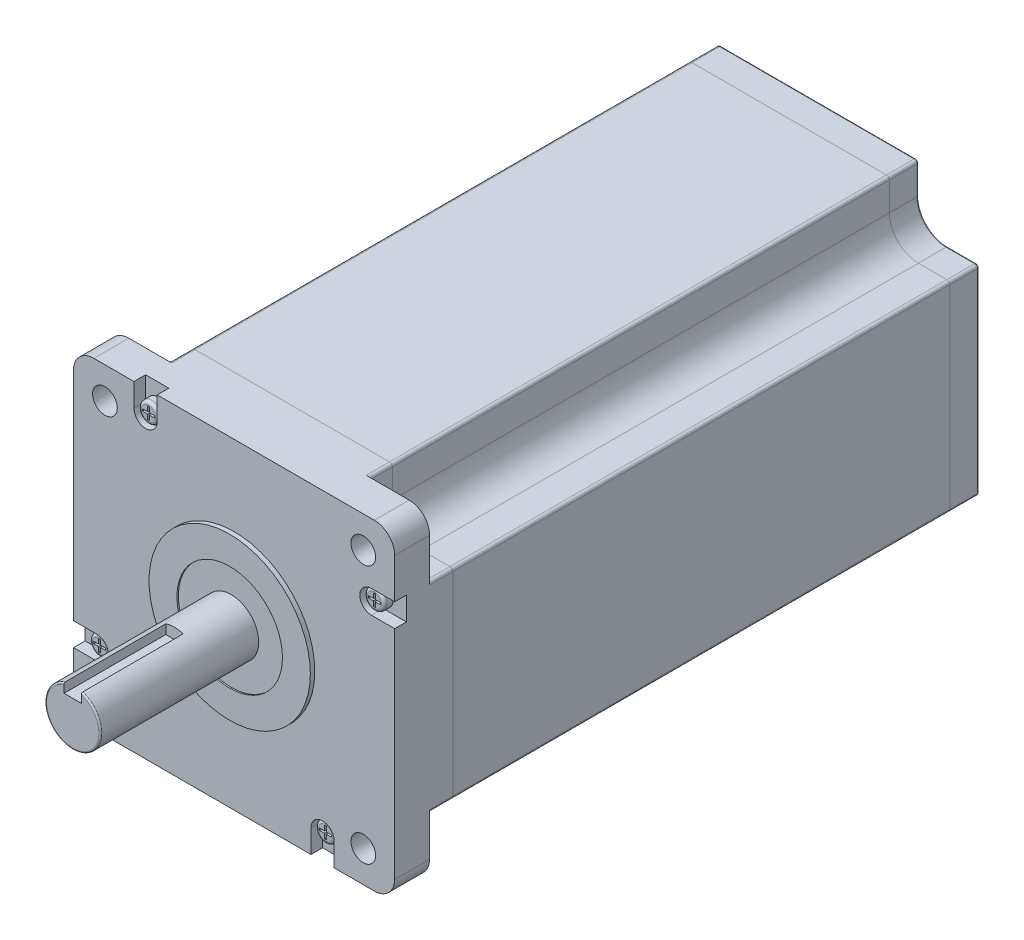
SolidWorks part; units mm, degrees
ref_plane "Front Plane" through (0, 0, 0) normal (0, 0, 1) x (1, 0, 0)
ref_plane "Top Plane" through (0, 0, 0) normal (0, 1, 0) x (1, 0, 0)
ref_plane "Right Plane" through (0, 0, 0) normal (1, 0, 0) x (0, 0, -1)
sketch "Sketch1" plane through (0, 0, 0) normal (0, 0, 1) x (1, 0, 0)
  line L0 (0, 55.25) -> (0, -55.25) construction
  line L1 (-48.25, -55.25) -> (48.25, -55.25)
  line L2 (-55.25, -48.25) -> (-55.25, 48.25)
  line L3 (-48.25, 55.25) -> (48.25, 55.25)
  line L4 (55.25, -48.25) -> (55.25, 48.25)
  line L5 (-55.25, -55.25) -> (55.25, 55.25) construction
  line L6 (-55.25, 55.25) -> (55.25, -55.25) construction
  circle A0 centre (-44.45, 44.45) radius 4.25
  circle A1 centre (44.45, 44.45) radius 4.25
  circle A2 centre (-44.45, -44.45) radius 4.25
  circle A3 centre (44.45, -44.45) radius 4.25
  arc A4 (48.25, -55.25) -> (55.25, -48.25) centre (48.25, -48.25) ccw
  arc A5 (-48.25, -55.25) -> (-55.25, -48.25) centre (-48.25, -48.25) cw
  arc A6 (48.25, 55.25) -> (55.25, 48.25) centre (48.25, 48.25) cw
  arc A7 (-55.25, 48.25) -> (-48.25, 55.25) centre (-48.25, 48.25) cw
  point P0 (0, 0)
  dimension "D3" = 8.5
  dimension "D8" = 7
  dimension "D1" = 110.5
  dimension "D2" = 110.5
  dimension "D4" = 88.9
  dimension "D5" = 88.9
  dimension "D6" = 44.45
  dimension "D7" = 44.45
extrude "Boss-Extrude1" add sketch "Sketch1" along normal blind 201
sketch "Sketch2" plane through (0, 0, 201) normal (0, 0, 1) x (1, 0, 0)
  circle A0 centre (0, 0) radius 27.75
  dimension "D1" = 55.5
extrude "Boss-Extrude2" add sketch "Sketch2" along normal blind 1.52
sketch "Sketch3" plane through (0, 0, 202.52) normal (0, 0, 1) x (1, 0, 0)
  circle A0 centre (0, 0) radius 9.5
  dimension "D1" = 19
extrude "Boss-Extrude3" add sketch "Sketch3" along normal blind 54 and the other way blind 1 separate body
sketch "Sketch4" plane through (0, 0, 256.52) normal (0, 0, 1) x (1, 0, 0)
  line L1 (-3, 11.8139) -> (3, 11.8139)
  line L2 (-3, 11.8139) -> (-3, 5.8139)
  line L3 (-3, 5.8139) -> (3, 5.8139)
  line L4 (3, 11.8139) -> (3, 5.8139)
  circle A1 centre (0, 0) radius 9.5 construction
  point P5 (0, 5.8139)
  point P6 (3, 9.0139)
  dimension "D1" = 6
  dimension "D2" = 6
  dimension "D3" = 2.8
extrude "Cut-Extrude1" cut sketch "Sketch4" against normal blind 35 and the other way blind 10
fillet "Fillet1" radius 0.5 1 edges at (0, -9.5, 256.52)
sketch "Sketch5" plane through (0, 0, 202.52) normal (0, 0, 1) x (1, 0, 0)
  circle A0 centre (0, 0) radius 18.1505
  dimension "D1" = 36.3009
extrude "Cut-Extrude2" cut sketch "Sketch5" against normal blind 0.5
sketch "Sketch6" plane through (0, 0, 0) normal (0, 0, -1) x (-1, 0, 0)
  line L0 (55.25, -34.45) -> (44.45, -34.45)
  line L3 (55.25, 48.25) -> (55.25, -48.25) construction
  line L6 (34.45, -44.45) -> (34.45, -55.25)
  line L7 (48.25, -55.25) -> (-48.25, -55.25) construction
  line L8 (34.45, -55.25) -> (48.25, -55.25)
  line L9 (55.25, -48.25) -> (55.25, -34.45)
  arc A0 (44.45, -34.45) -> (34.45, -44.45) centre (44.45, -44.45) ccw
  arc A2 (48.25, -55.25) -> (55.25, -48.25) centre (48.25, -48.25) ccw
  circle A3 centre (44.45, -44.45) radius 4.25 construction
  dimension "D1" = 10
extrude "Cut-Extrude3" cut sketch "Sketch6" against normal offset from surface (189 mm away) 12 up to face at (48.7, -44.45, 201)
mirror "Mirror1" about plane through (0, 0, 0) normal (1, 0, 0) of "Cut-Extrude3"
mirror "Mirror2" about plane through (0, 0, 0) normal (0, 1, 0) of "Mirror1", "Cut-Extrude3"
sketch "Sketch7" plane through (0, 55.25, 0) normal (0, 1, 0) x (1, 0, 0)
  line L0 (-55.25, -181) -> (55.25, -181)
  line L1 (-55.25, -10) -> (55.25, -10)
  line L2 (34.45, 0) -> (-34.45, 0) construction
  line L3 (48.25, -201) -> (-48.25, -201) construction
  line L4 (-55.25, -189) -> (-55.25, 0) construction
  line L5 (55.25, -189) -> (55.25, 0) construction
  dimension "D1" = 10
  dimension "D2" = 20
split line "Split Line3"
fillet "Fillet2" radius 0.5 16 edges at (-55.25, 0, 0) (-49.85, 34.45, 0) (-37.3789, 37.3789, 0) (-34.45, 49.85, 0) (0, -55.25, 0) (-49.85, -34.45, 0) (-37.3789, -37.3789, 0) (-34.45, -49.85, 0) (55.25, 0, 0) (49.85, -34.45, 0) (37.3789, -37.3789, 0) (34.45, -49.85, 0) (0, 55.25, 0) (49.85, 34.45, 0) (37.3789, 37.3789, 0) (34.45, 49.85, 0)
fillet "Fillet3" radius 1 32 edges at (-55.25, 34.45, 185) (-34.45, 55.25, 185) (-55.25, 34.45, 95.5) (-55.25, -34.45, 95.5) (-34.45, 55.25, 95.5) (34.45, 55.25, 95.5) (55.25, 34.45, 95.5) (55.25, -34.45, 95.5) (34.45, -55.25, 95.5) (-34.45, -55.25, 95.5) (-34.45, 55.25, 5.25) (-55.25, 34.45, 5.25) (34.45, 55.25, 5.25) (55.25, 34.45, 5.25) (34.45, -55.25, 5.25) (55.25, -34.45, 5.25) (-34.45, -55.25, 5.25) (-55.25, -34.45, 5.25) (55.1036, 34.3036, 0.1464) (55.1036, -34.3036, 0.1464) (34.3036, 55.1036, 0.1464) (34.3036, -55.1036, 0.1464) (-34.3036, 55.1036, 0.1464) (-34.3036, -55.1036, 0.1464) (-55.1036, 34.3036, 0.1464) (-55.1036, -34.3036, 0.1464) (-34.45, -55.25, 185) (-55.25, -34.45, 185) (55.25, -34.45, 185) (34.45, -55.25, 185) (34.45, 55.25, 185) (55.25, 34.45, 185)
sketch "Sketch8" plane through (0, 0, 0) normal (0, 0, -1) x (-1, 0, 0)
  circle A0 centre (0, 0) radius 17.5
  dimension "D1" = 35
extrude "Cut-Extrude4" cut sketch "Sketch8" against normal blind 1
sketch "Sketch9" plane through (0, 0, 1) normal (0, 0, -1) x (-1, 0, 0)
  circle A0 centre (0, 0) radius 9.5
  dimension "D1" = 19
extrude "Boss-Extrude4" add sketch "Sketch9" along normal blind 0.8 separate body
sketch "Sketch10" plane through (0, 0, 201) normal (0, 0, 1) x (1, 0, 0)
  line L0 (-34.45, 47.25) -> (-34.45, 55.25)
  line L1 (48.25, 55.25) -> (-48.25, 55.25) construction
  line L2 (-34.45, 55.25) -> (-26.45, 55.25)
  line L3 (-26.45, 55.25) -> (-26.45, 47.25)
  line L4 (47.25, 34.45) -> (55.25, 34.45)
  line L5 (55.25, 34.45) -> (55.25, 26.45)
  line L6 (55.25, 26.45) -> (47.25, 26.45)
  line L7 (34.45, -47.25) -> (34.45, -55.25)
  line L8 (34.45, -55.25) -> (26.45, -55.25)
  line L9 (26.45, -55.25) -> (26.45, -47.25)
  line L10 (-47.25, -34.45) -> (-55.25, -34.45)
  line L11 (-55.25, -34.45) -> (-55.25, -26.45)
  line L12 (-55.25, -26.45) -> (-47.25, -26.45)
  line L13 (55.25, -48.25) -> (55.25, 48.25) construction
  line L14 (-55.25, 48.25) -> (-55.25, -48.25) construction
  arc A0 (-34.45, 47.25) -> (-26.45, 47.25) centre (-30.45, 47.25) ccw
  arc A1 (47.25, 34.45) -> (47.25, 26.45) centre (47.25, 30.45) ccw
  arc A2 (34.45, -47.25) -> (26.45, -47.25) centre (30.45, -47.25) ccw
  arc A3 (-47.25, -34.45) -> (-47.25, -26.45) centre (-47.25, -30.45) ccw
  circle A4 centre (-44.45, 44.45) radius 4.25 construction
  point P25 (0, 0)
  dimension "D1" = 8
  dimension "D3" = 8
  dimension "D4" = 10
  dimension "D2" = 4
extrude "Cut-Extrude5" cut sketch "Sketch10" against normal blind 4
sketch "Sketch11" plane through (0, 0, 197) normal (0, 0, 1) x (1, 0, 0)
  circle A0 centre (-30.45, 47.25) radius 3.4342
  point P12 (0, 0)
extrude "Boss-Extrude5" add sketch "Sketch11" along normal blind 3 separate body
fillet "Fillet4" radius 1 1 edges at (-27.0158, 47.25, 200)
sketch "Sketch12" plane through (0, 0, 200) normal (0, 0, 1) x (1, 0, 0)
  line L0 (-30.0997, 47.6) -> (-28.3929, 47.6)
  line L1 (-30.8003, 45.1907) -> (-30.0997, 45.1907)
  line L2 (-30.8003, 45.1907) -> (-30.8003, 46.9)
  line L3 (-30.8003, 49.3093) -> (-30.0997, 49.3093)
  line L4 (-30.0997, 45.1907) -> (-30.0997, 46.9)
  line L5 (-30.8003, 45.1907) -> (-30.0997, 49.3093) construction
  line L6 (-30.8003, 49.3093) -> (-30.0997, 45.1907) construction
  line L7 (-32.5071, 47.6) -> (-30.8003, 47.6)
  line L8 (-32.5071, 47.6) -> (-32.5071, 46.9)
  line L9 (-32.5071, 46.9) -> (-30.8003, 46.9)
  line L10 (-28.3929, 47.6) -> (-28.3929, 46.9)
  line L11 (-32.5071, 47.6) -> (-28.3929, 46.9) construction
  line L12 (-32.5071, 46.9) -> (-28.3929, 47.6) construction
  line L13 (-30.0997, 46.9) -> (-28.3929, 46.9)
  line L14 (-30.8003, 47.6) -> (-30.8003, 49.3093)
  line L15 (-30.0997, 47.6) -> (-30.0997, 49.3093)
  point P0 (-30.45, 47.25)
  point P6 (-30.45, 47.25)
extrude "Cut-Extrude6" cut sketch "Sketch12" against normal blind 2 draft 6
chamfer "Chamfer2" distance 1.5 angle 45 4 edges at (-30.45, 45.4009, 198) (-30.45, 49.0991, 198) (-28.6031, 47.25, 198) (-32.2969, 47.25, 198)
pattern_circular "CirPattern3" count 4 over 360 about axis through (0, 0, 0) along (0, 0, 1) of bodies 115
equation "\"D6@Sketch1\"=\"D5@Sketch1\"/2"
equation "\"D7@Sketch1\"=\"D4@Sketch1\"/2"
equation "\"D1@Sketch1\"=\"D2@Sketch1\""
